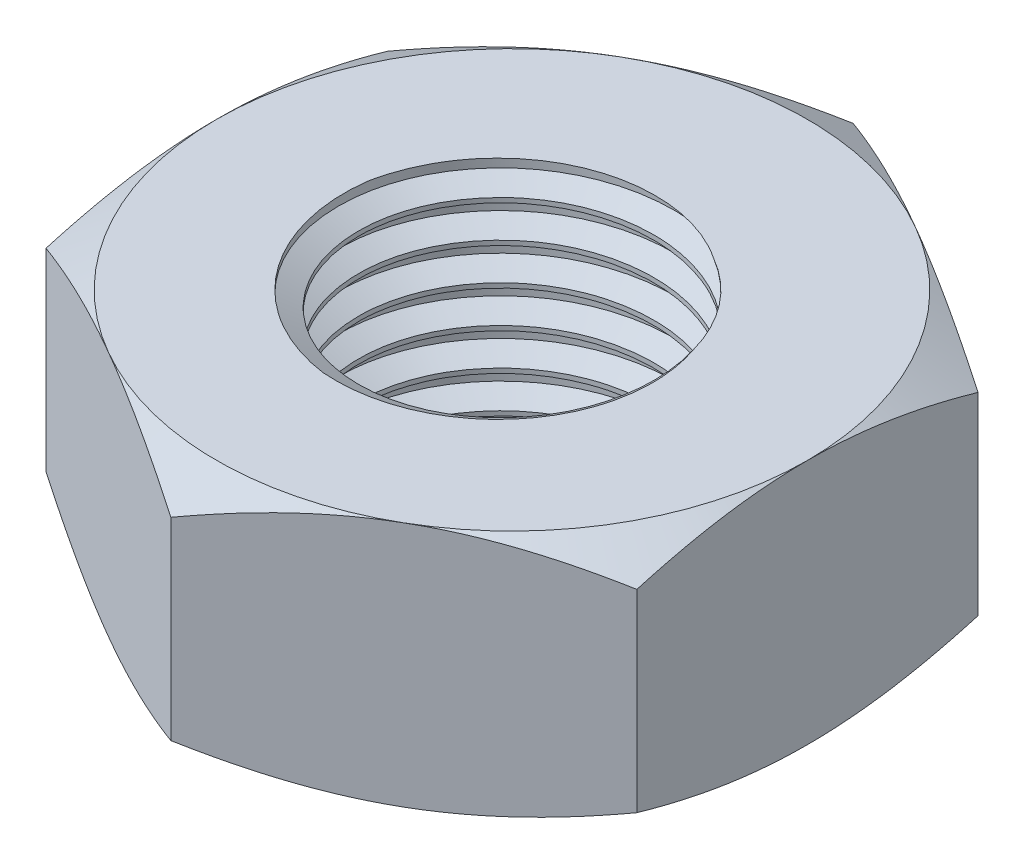
SolidWorks part; units mm, degrees
ref_plane "Front Plane" through (0, 0, 0) normal (0, 0, 1) x (1, 0, 0)
ref_plane "Top Plane" through (0, 0, 0) normal (0, 1, 0) x (1, 0, 0)
ref_plane "Right Plane" through (0, 0, 0) normal (1, 0, 0) x (0, 0, -1)
sketch "Sketch1" plane through (0, 0, 0) normal (0, 1, 0) x (1, 0, 0)
  line L1 (0, 13.8564) -> (-12, 6.9282)
  line L2 (-12, 6.9282) -> (-12, -6.9282)
  line L3 (-12, -6.9282) -> (0, -13.8564)
  line L4 (0, -13.8564) -> (12, -6.9282)
  line L5 (12, -6.9282) -> (12, 6.9282)
  line L6 (12, 6.9282) -> (0, 13.8564)
  circle A0 centre (0, 0) radius 12 construction
  circle A1 centre (0, 0) radius 6
  dimension "D2" = 12
  dimension "D1" = 24
extrude "Boss-Extrude1" add sketch "Sketch1" along normal mid plane 10
sketch "Sketch2" plane through (0, 5, 0) normal (0, 1, 0) x (1, 0, 0)
  line L0 (-12, 6.9282) -> (-12, -6.9282) construction
  circle A0 centre (0, 0) radius 12
extrude "Cut-Extrude1" cut sketch "Sketch2" against normal through all both draft 60 and the other way through all flip side to cut
mirror "Mirror1" about plane through (0, 0, 0) normal (0, 1, 0) of "Cut-Extrude1"
thread "Thread1" pitch 1.5 method cut profile "Thread Profile1" start angle 0, offset 5, length 27, pitch 1.5, diameter 12
ref_plane "Plane1" through (-6, 10, 0) normal (0, 0, -1) x (1, 0, 0)
sketch "Thread Profile1" plane through (-6, 10, 0) normal (0, 0, -1) x (1, 0, 0)
  line L0 (0, 0) -> (0, 1.5) construction
  line L11 (0, 0) -> (0, 1.3125)
  line L12 (0, 1.3125) -> (-0.8119, 0.8437)
  line L13 (-0.8119, 0.8437) -> (-0.8119, 0.4687)
  line L15 (-0.8119, 0.4687) -> (0, 0)
  line L17 (-0.8119, 0.6562) -> (0, 0.6562) construction
  point P2 (0, 0)
  dimension "Pitch" = 1.5
  dimension "Profile_Angle" = 60
  dimension "Profile_Land" = 0.375
  dimension "Profile_Height" = 0.8119
